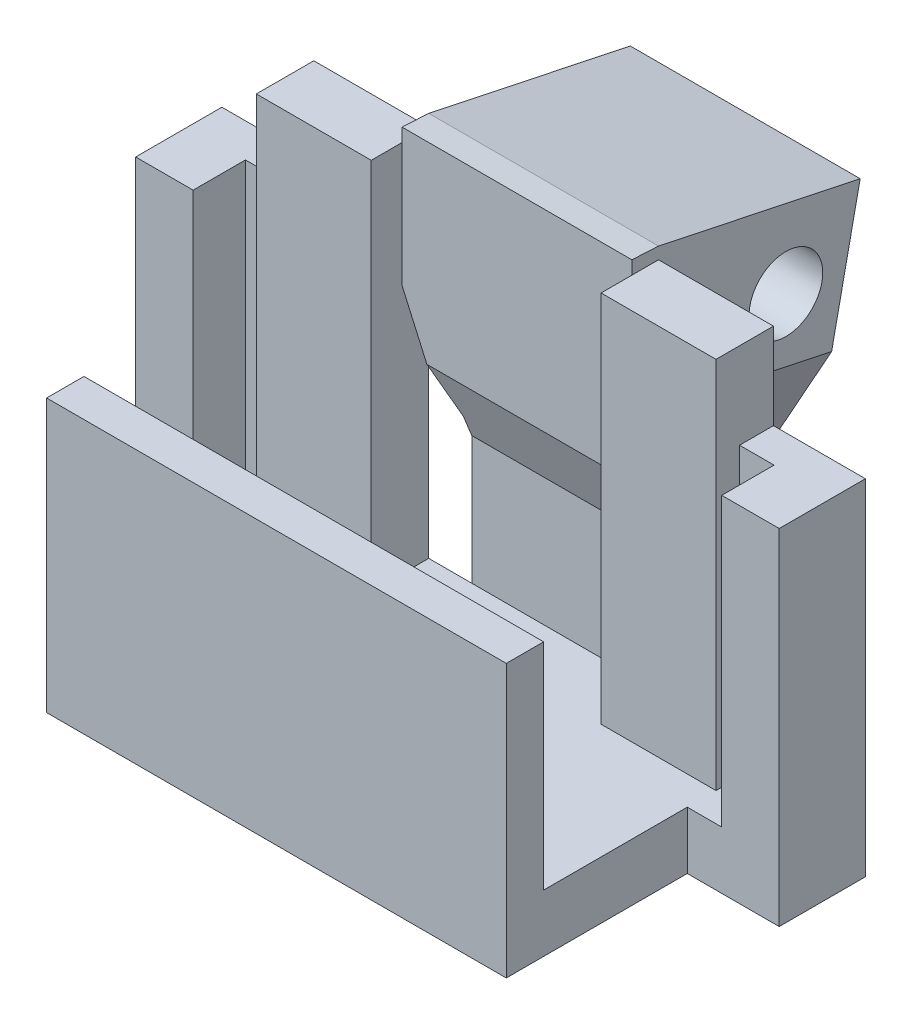
SolidWorks part; units mm, degrees
ref_plane "前视基准面" through (0, 0, 0) normal (0, 0, 1) x (1, 0, 0)
ref_plane "上视基准面" through (0, 0, 0) normal (0, 1, 0) x (1, 0, 0)
ref_plane "右视基准面" through (0, 0, 0) normal (1, 0, 0) x (0, 0, -1)
sketch "草图1" plane through (0, 0, 0) normal (0, 1, 0) x (1, 0, 0)
  line L1 (8, -4.75) -> (-8, -4.75)
  line L2 (8, -4.75) -> (8, 4.75)
  line L3 (8, 4.75) -> (-8, 4.75)
  line L4 (-8, -4.75) -> (-8, 4.75)
  line L5 (8, -4.75) -> (-8, 4.75) construction
  line L6 (8, 4.75) -> (-8, -4.75) construction
  line L7 (8, 4.75) -> (-8, 4.75)
  line L8 (8, 4.75) -> (8, 2.75)
  line L9 (8, 2.75) -> (-8, 2.75)
  line L10 (-8, 4.75) -> (-8, 2.75)
  line L11 (8, -4.75) -> (-8, -4.75)
  line L12 (8, -4.75) -> (8, -3.25)
  line L13 (8, -3.25) -> (-8, -3.25)
  line L14 (-8, -4.75) -> (-8, -3.25)
  point P0 (0, 0)
  dimension "D1" = 6
  dimension "D2" = 9.5
  dimension "D3" = 2
  dimension "D4" = 16
extrude "凸台-拉伸1" add sketch "草图1" along normal blind 2 contours L13 L2 L9 L4 region at (0, 0, 0.25)
extrude "凸台-拉伸2" add sketch "草图1<3>" along normal blind 15 contours L9 L2 L3 L4 | L2 L13 L4 L1 region at (0, 0, 4) region at (0, 0, -3.75)
sketch "草图1<3>" plane through (0, 0, 0) normal (0, 1, 0) x (1, 0, 0) same geometry as "草图1"
sketch "草图2" plane through (0, 0, -4.75) normal (0, 0, -1) x (-1, 0, 0)
  line L0 (0, 12.199) -> (0, -4.867) construction
  line L1 (-8, 15) -> (8, 15) construction
  line L2 (4, 28) -> (-4, 28)
  line L3 (4, 28) -> (4, 2)
  line L4 (4, 2) -> (-4, 2)
  line L5 (-4, 28) -> (-4, 2)
  line L6 (4, 28) -> (-4, 2) construction
  line L7 (4, 2) -> (-4, 28) construction
  line L8 (-8, 2) -> (8, 2) construction
  point P3 (0, 15)
  dimension "D1" = 8
  dimension "D2" = 0
extrude "切除-拉伸1" cut sketch "草图2" against normal up to surface (2 mm away) up to face at (0, 8.5, -2.75)
sketch "草图3" plane through (0, 0, 0) normal (1, 0, 0) x (0, 0, -1)
  line L0 (4.75, 0) -> (8.8316, 0)
  line L3 (4.75, 15.4148) -> (4.75, 0)
  line L4 (4.75, 15.4148) -> (11.7685, 13.9357)
  line L5 (11.7685, 13.9357) -> (8.8316, 0)
  dimension "D1" = 90
extrude "凸台-拉伸3" add sketch "草图3" along normal mid plane 5
sketch "草图4" plane through (8, 0, 0) normal (1, 0, 0) x (0, 0, -1)
  line L0 (2.75, 15) -> (2.75, 2) construction
  line L1 (4.75, 15) -> (2.75, 15)
  line L2 (4.75, 15) -> (4.75, 11.7656)
  line L3 (4.75, 11.7656) -> (2.75, 11.7656)
  line L4 (2.75, 15) -> (2.75, 11.7656)
sketch "草图5" plane through (2.5, 0, 0) normal (1, 0, 0) x (0, 0, -1)
  line L0 (4.75, 6.4511) -> (3.8228, 8.745)
  line L1 (4.75, 15) -> (4.75, 0) construction
  line L2 (3.8228, 8.745) -> (3.8228, 15.4638)
  line L3 (2.7617, 15.5198) -> (10.7506, 15.0981) construction
  line L4 (3.8228, 15.4638) -> (4.75, 15.4148)
  line L5 (4.75, 15.4148) -> (4.75, 6.4511)
extrude "凸台-拉伸4" add sketch "草图5" against normal up to surface (5 mm away) up to face at (-2.5, 6.2701, -6.97)
sketch "草图6" plane through (-2.5, 0, 0) normal (-1, 0, 0) x (0, 0, 1)
  line L0 (-4.75, 6.4511) -> (-10.0949, 5.9946)
  line L7 (-4.75, 2) -> (-4.75, 6.4511)
  line L8 (-4.75, 6.4511) -> (-3.8228, 8.745)
  line L9 (-3.8228, 8.745) -> (-3.8228, 15.4638)
  line L10 (-3.8228, 15.4638) -> (-4.75, 15.4148)
  line L11 (-3.8228, 15.4638) -> (-4.75, 15.4148)
  line L12 (-8.8316, 0) -> (-4.75, 0)
  line L13 (-4.75, 0) -> (-4.75, 2)
  line L15 (-4.75, 6.4511) -> (-3.8228, 8.745)
  line L16 (-3.8228, 8.745) -> (-3.8228, 15.4638)
  line L22 (-4.75, 15.4148) -> (-11.7685, 13.9357)
  line L23 (-4.75, 15.4148) -> (-11.7685, 13.9357)
  line L24 (-11.7685, 13.9357) -> (-8.8316, 0)
  line L25 (-11.7685, 13.9357) -> (-10.0949, 5.9946)
  dimension "D1" = 0
extrude "凸台-拉伸5" add sketch "草图6" along normal up to surface (1.5 mm away) up to face at (-4, 8.5, -3.75)
sketch "草图9" plane through (0, 0, 0) normal (0, -1, 0) x (1, 0, 0)
  line L0 (8, -4.75) -> (11.2, -4.75)
  line L1 (11.2, -4.75) -> (11.2, -1.75)
  line L2 (11.2, -1.75) -> (9.2, -1.75)
  line L4 (8, -3.5704) -> (8, -4.75)
  line L5 (9.2, -1.75) -> (9.2, -3.5704)
  line L6 (9.2, -3.5704) -> (8, -3.5704)
  line L7 (9.2, -1.75) -> (8, -1.75)
  line L8 (8, 4.75) -> (8, -4.75) construction
  line L9 (8, -1.75) -> (8, -3.5704)
  line L10 (0, 0) -> (0, -12.5877) construction
  line L11 (-8, -1.75) -> (-8, -3.5704)
  line L12 (-9.2, -1.75) -> (-8, -1.75)
  line L13 (-9.2, -3.5704) -> (-8, -3.5704)
  line L14 (-9.2, -1.75) -> (-9.2, -3.5704)
  line L15 (-8, -3.5704) -> (-8, -4.75)
  line L16 (-11.2, -1.75) -> (-9.2, -1.75)
  line L17 (-11.2, -4.75) -> (-11.2, -1.75)
  line L18 (-8, -4.75) -> (-11.2, -4.75)
  line M7 (8, -4.75) -> (8, 4.75)
  line M9 (-8, 4.75) -> (-8, -4.75)
  dimension "D1" = 3
  dimension "D2" = 1.2
  dimension "D3" = 2
extrude "凸台-拉伸6" add sketch "草图9" against normal up to surface (2 mm away) contours L5 L7 L6 M7 | L12 L14 L13 M9 region at (8.6, 0, -2.6602) region at (-8.6, 0, -2.6602) up to face at (0, 2, -2.35)
extrude "凸台-拉伸7" add sketch "草图9<3>" against normal blind 12 contours L5 L6 L0 L1 L2 M7 | L18 L13 L14 L16 L17 M9 region at (9.8946, 0, -3.4237) region at (-9.8946, 0, -3.4237)
sketch "草图9<3>" plane through (0, 0, 0) normal (0, -1, 0) x (1, 0, 0) same geometry as "草图9"
sketch "草图11" plane through (0, -1.7821, -8.456) normal (0, -0.2062, -0.9785) x (-1, 0, 0)
  line L0 (2.5, 7.9475) -> (4, 11.2453)
  line L1 (4, 16.063) -> (4, 7.9475) construction
  line L2 (4, 11.2453) -> (4, 7.9475)
  line L4 (4, 7.9475) -> (4, 5.815)
  line L5 (4, 5.815) -> (2.5, 5.815)
  line L6 (2.5, 5.815) -> (2.5, 7.9475)
extrude "切除-拉伸2" cut sketch "草图11" against normal up to surface (5.9605 mm away) up to face at (-1.4, 12.6835, -3.8228)
mirror "镜向1" about plane through (0, 0, 0) normal (1, 0, 0) of "凸台-拉伸5", "切除-拉伸2"
sketch "草图12" plane through (4, 0, 0) normal (1, 0, 0) x (0, 0, -1)
  circle A0 centre (9.1836, 11.7521) radius 1.2818
extrude "切除-拉伸3" cut sketch "草图12" against normal blind 10
sketch "草图13" plane through (8, 0, 0) normal (1, 0, 0) x (0, 0, -1)
  line L0 (-3.25, 9.4845) -> (-4.55, 9.4845)
  line L1 (-3.25, 15) -> (-3.25, 2) construction
  line L2 (-4.55, 9.4845) -> (-4.55, 0)
  line L3 (-4.75, 0) -> (1.75, 0) construction
  line L4 (-4.55, 0) -> (-4.75, 0)
  line L5 (-4.75, 0) -> (-4.75, 15)
  line L6 (-4.75, 15) -> (-3.25, 15)
  line L7 (-4.75, 15) -> (-3.25, 15) construction
  line L8 (-3.25, 15) -> (-3.25, 9.4845)
  dimension "D1" = 1.3
extrude "切除-拉伸4" cut sketch "草图13" against normal through all
